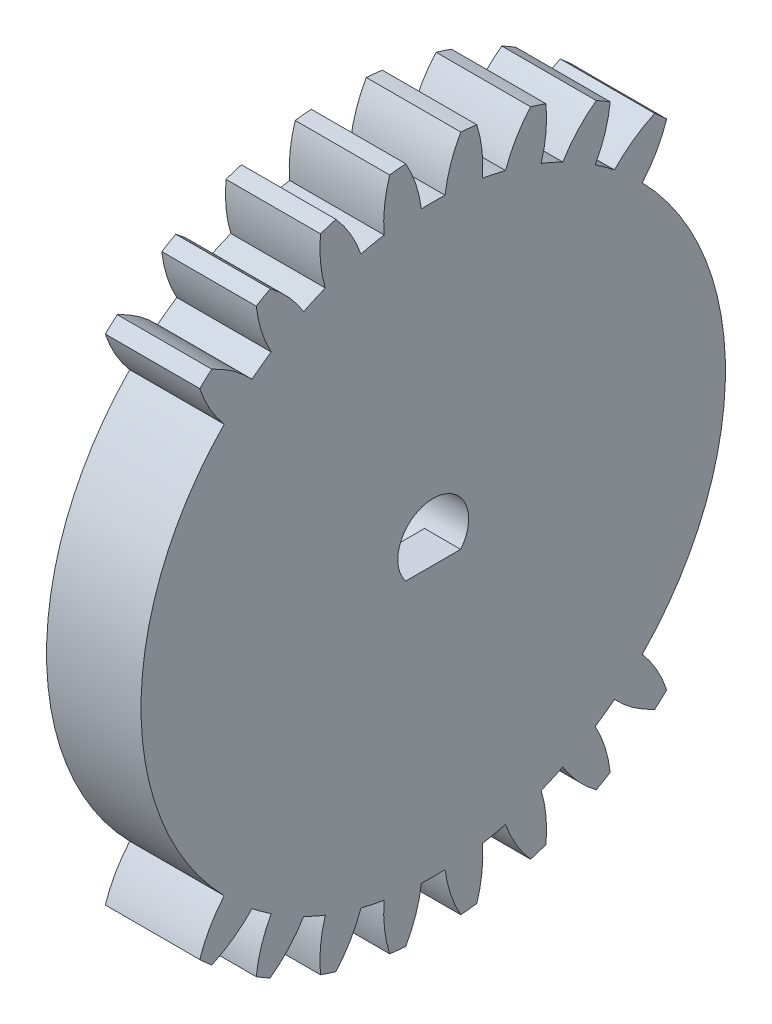
SolidWorks part; units mm, degrees
ref_plane "Plane1" through (0, 0, 0) normal (0, 0, 1) x (1, 0, 0)
ref_plane "Plane2" through (0, 0, 0) normal (0, 1, 0) x (1, 0, 0)
ref_plane "Plane3" through (0, 0, 0) normal (1, 0, 0) x (0, 0, -1)
other "Configuration Table"
sketch "HoldingSke" plane through (0, 0, 0) normal (0, 1, 0) x (1, 0, 0)
  line L0 (0, 0) -> (1.0373, -0.3982)
  line L1 (-15, 0) -> (100, 0) construction
  line L2 (0, 0) -> (-2.1039, 2.3779)
  line L3 (0, 0) -> (-11.863, 4.5341)
  line L4 (0, 0) -> (7.479, 4.318)
  line L5 (0, 0) -> (-46.8476, -17.4728)
  line L6 (0, 0) -> (-8.2896, -5.593)
  line L7 (-2.1039, 2.3779) -> (8.6586, 51.2059)
  line L8 (-76.2, 54.61) -> (-75.5, 54.61)
  line L9 (-67.7845, 28.3722) -> (-49.3413, 33.142)
  line L10 (-76.2, 71.12) -> (104.1128, 71.12)
  line L11 (0, 0) -> (-10, 0)
  line L12 (-76.2, 101.6) -> (-76.166, 101.6)
  line L13 (24.9733, 27.94) -> (52.9518, 28.4284)
  line L14 (24.9733, 27.94) -> (24.9743, 27.94)
  line L15 (24.9733, 27.94) -> (100.4006, 29.5858)
  line L16 (-63.627, -0.9) -> (-12.827, -0.9)
  circle A0 centre (0, 0) radius 2
  circle A1 centre (0, 0) radius 12.374
  circle A2 centre (0, 0) radius 37.5
  circle A3 centre (0, 0) radius 2
  dimension "Num_teeth" = 30
  dimension "Pitch_radius" = 180.3128
  dimension "Width" = 10
sketch "BasProSke" plane through (0, 0, 0) normal (0, 1, 0) x (1, 0, 0)
  line L0 (-10, 0) -> (60, 0) construction
  line L1 (0, 0) -> (0, 14.4)
  line L2 (0, 0) -> (4, 0)
  line L3 (4, 0) -> (4, 14.4)
  line L4 (4, 14.4) -> (0, 14.4)
  dimension "D1" = 4
  dimension "Diameter" = 28.8
revolve "Base-Revolve" add sketch "BasProSke" angle 360 about L0
sketch "TooCutSke" plane through (0, 0, 0) normal (1, 0, 0) x (0, 0, -1)
  line L1 (0, 0) -> (0, 107) construction
  line L2 (0, 0) -> (-0.766, 13.4782) construction
  line L3 (0, 0) -> (-2.819, 26.8212) construction
  line L4 (-0.766, 13.4782) -> (-1.4095, 13.4106) construction
  arc A0 (0.502, 12.3638) -> (-0.502, 12.3638) centre (0, 0) ccw
  arc A1 (1.1789, 14.3771) -> (-1.1789, 14.3771) centre (0, 0) ccw
  circle A2 centre (0, 0) radius 13.5 construction
  circle A3 centre (0, 0) radius 13.07 construction
  arc A4 (-0.502, 12.3638) -> (-1.1789, 14.3771) centre (-5.8589, 11.6832) ccw
  arc A5 (1.1789, 14.3771) -> (0.502, 12.3638) centre (5.8589, 11.6832) ccw
extrude "ToothCut" cut sketch "TooCutSke" along normal through all
fillet "Breaks" [suppressed] radius 0.018 tangent propagation no
fillet "RootFillets" [suppressed] radius 0.226
pattern_circular "TeethCuts" count 30 every 12 about axis through (-10, 0, 0) along (1, 0, 0) of "ToothCut"
sketch "HubNeaOneSke" plane through (0, 0, 0) normal (-1, 0, 0) x (0, 0, 1)
  circle A0 centre (0, 0) radius 12.374
  dimension "Diameter" = 24.748
extrude "HubNearOne" [suppressed] add sketch "HubNeaOneSke" along normal blind 40.0001
sketch "HubNeaBotSke" plane through (0, 0, 0) normal (-1, 0, 0) x (0, 0, 1)
  circle A0 centre (0, 0) radius 12.374
  dimension "Diameter" = 24.748
extrude "HubNearBoth" [suppressed] add sketch "HubNeaBotSke" along normal blind 20
ref_plane "FarPln" through (10, 0, 0) normal (1, 0, 0) x (0, 0, -1)
sketch "HubFarSke" plane through (10, 0, 0) normal (1, 0, 0) x (0, 0, -1)
  circle A0 centre (0, 0) radius 12.374
  dimension "Diameter" = 24.748
extrude "HubFar" [suppressed] add sketch "HubFarSke" along normal blind 20
sketch "BorSke" plane through (0, 0, 0) normal (1, 0, 0) x (0, 0, -1)
  line L0 (-1.1608, -0.95) -> (1.1608, -0.95)
  line L1 (0, 1.5) -> (0, -0.95) construction
  arc A0 (1.1608, -0.95) -> (-1.1608, -0.95) centre (0, 0) ccw
  dimension "D1" = 2.45
  dimension "Diameter" = 3
extrude "Bore" cut sketch "BorSke" along normal mid plane 100.0001
sketch "KeySke" plane through (0, 0, 0) normal (1, 0, 0) x (0, 0, -1)
  line L0 (-0.8, 0) -> (-0.8, 2.7)
  line L1 (-0.8, 2.7) -> (0.8, 2.7)
  line L2 (0.8, 2.7) -> (0.8, 0)
  line L3 (0, 0) -> (0, 34) construction
  line L4 (-0.8, 0) -> (0.8, 0)
  dimension "Offset" = 2.7
  dimension "Width" = 1.6
extrude "Keyway" [suppressed] cut sketch "KeySke" along normal mid plane 100.0001
pattern_circular "Keyway2" [suppressed] count 2 every 90 about axis through (-10, 0, 0) along (1, 0, 0)
sketch "Sketch1" plane through (4, 0, 0) normal (1, 0, 0) x (0, 0, -1)
  line L4 (0, 12.374) -> (0, -12.374) construction
  line L9 (-9.1957, 8.2798) -> (-11.8374, 9.9904)
  line L10 (-9.0832, -8.4031) -> (-11.109, -10.7946)
  line L11 (9.0832, -8.4031) -> (11.109, -10.7946)
  line L12 (9.1957, 8.2798) -> (11.8374, 9.9904)
  arc A11 (0.502, 12.3638) -> (-0.502, 12.3638) centre (0, 0) ccw construction
  arc A12 (-0.502, -12.3638) -> (0.502, -12.3638) centre (0, 0) ccw construction
  arc A14 (-9.1957, 8.2798) -> (-9.0832, -8.4031) centre (0, 0) ccw
  arc A15 (-10.4564, 6.6167) -> (-10.9584, 5.7472) centre (0, 0) ccw construction
  arc A16 (-11.109, -10.7946) -> (-11.8374, 9.9904) centre (0, 0) cw
  arc A17 (-8.8522, 8.6461) -> (-9.524, 7.8999) centre (0, 0) ccw construction
  arc A18 (11.109, -10.7946) -> (11.8374, 9.9904) centre (0, 0) ccw
  arc A19 (9.1957, 8.2798) -> (9.0832, -8.4031) centre (0, 0) cw
extrude "Cut-Extrude2" cut sketch "Sketch1" against normal blind 10
sketch "Sketch3" plane through (0, 0, 0) normal (-1, 0, 0) x (0, 0, 1)
  circle A2 centre (0, 0) radius 1.5
  dimension "D1" = 3
extrude "Cut-Extrude3" cut sketch "Sketch3" against normal blind 2.47
equation "' \"Module@HoldingSke\" = 6.35"
equation "' \"Num_teeth@HoldingSke\" = 12"
equation "' \"Ap@HoldingSke\" =  20"
equation "' \"Ap@HoldingSke\" = 20"
equation "' \"Width@HoldingSke\" = 0.5 * 25.4"
equation "' \"Hub_dia@HoldingSke\"= 1 * 25.4"
equation "' \"Hub_dia@HoldingSke\" = 1 * 25.4"
equation "' \"Overall_len@HoldingSke\" = 1.0 * 25.4"
equation "' \"Bore@HoldingSke\" = 0.75 * 25.4"
equation "' \"T_dim@HoldingSke\" = 0.1 * 25.4"
equation "' \"Width@KeySke\" = 0.25 * 25.4"
equation "' \"Show_teeth@HoldingSke\" = 13"
equation "' \"Backlash@HoldingSke\" = 0.009 * 25.4"
equation "' \"Addendum_fac@HoldingSke\" = 1.0"
equation "' \"Dedendum_fac@HoldingSke\" = 1.25"
equation "' \"Dedendum_add@HoldingSke\" = 0.00005 * 25.4"
equation "' \"Clearance_fac@HoldingSke\" = 0.25"
equation "\"Pitch@HoldingSke\" = 1 / \"Module@HoldingSke\""
equation "\"Overcut_dia@TooCutSke\" = (\"Num_teeth@HoldingSke\" + 2 * \"Addendum_fac@HoldingSke\") / \"Pitch@HoldingSke\" + 0.002 * 25.4"
equation "\"Pitch_dia@TooCutSke\" = \"Num_teeth@HoldingSke\" / \"Pitch@HoldingSke\""
equation "\"Base_dia@TooCutSke\" = \"Num_teeth@HoldingSke\" / \"Pitch@HoldingSke\" * cos((\"Ap@HoldingSke\"  * 3.14159265 / 180))"
equation "\"Root_dia@TooCutSke\" = (\"Num_teeth@HoldingSke\" + 2) / \"Pitch@HoldingSke\" - 2 * (\"Addendum_fac@HoldingSke\" + \"Dedendum_fac@HoldingSke\") / \"Pitch@HoldingSke\" - \"Dedendum_add@HoldingSke\" * 2"
equation "\"Half_ang@TooCutSke\" = 180 / \"Num_teeth@HoldingSke\""
equation "\"Half_CT@TooCutSke\" = \"Num_teeth@HoldingSke\" / \"Pitch@HoldingSke\" * sin((3.14159265 / 2 / \"Num_teeth@HoldingSke\")) / 2 - 7 * \"Backlash@HoldingSke\" / 4"
equation "\"Flank_rad@TooCutSke\" = \"Num_teeth@HoldingSke\" / \"Pitch@HoldingSke\" / 5"
equation "\"Radius@RootFillets\" = \"Clearance_fac@HoldingSke\" / \"Pitch@HoldingSke\" + \"Dedendum_add@HoldingSke\""
equation "\"Break_rad@Breaks\" = 0.02 / \"Pitch@HoldingSke\""
equation "\"Thickness@HoldingSke\" = \"Width@HoldingSke\""
